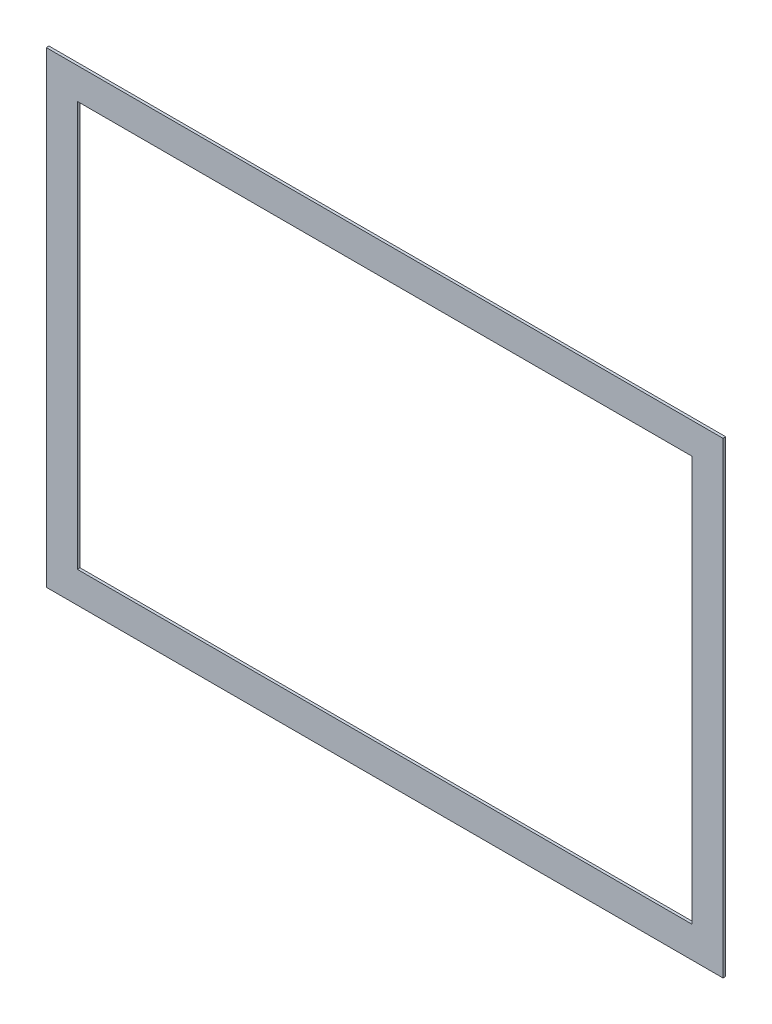
SolidWorks part; units mm, degrees
ref_plane "Front Plane" through (0, 0, 0) normal (0, 0, 1) x (1, 0, 0)
ref_plane "Top Plane" through (0, 0, 0) normal (0, 1, 0) x (1, 0, 0)
ref_plane "Right Plane" through (0, 0, 0) normal (1, 0, 0) x (0, 0, -1)
sketch "Çizim1" plane through (0, 0, 0) normal (0, 0, 1) x (1, 0, 0)
  line L0 (-23, 323) -> (478, 323)
  line L1 (0, 300) -> (455, 300)
  line L2 (0, 300) -> (0, 0)
  line L3 (0, 0) -> (455, 0)
  line L4 (455, 300) -> (455, 0)
  line L5 (478, 323) -> (478, -23)
  line L6 (-23, -23) -> (478, -23)
  line L7 (-23, 323) -> (-23, -23)
  dimension "D1" = 455
  dimension "D2" = 300
  dimension "D3" = 23
base flange "Taban-Flanş1" sketch "Çizim1" thickness 2 reverse thickness direction no parameters "D1"=0.7366
sketch "Büküm-Çizgileri1" [suppressed] plane through (0, 0, 0) normal (0, 1, 0) x (1, 0, 0)
sketch "Sınırlandırma-Kutusu1" [suppressed] plane through (0, 0, 0) normal (0, 1, 0) x (1, 0, 0)
sheet metal parameters "Sac-Levha1" thickness 2 parameters "D1"=0.7366
flat pattern "Düz-Çoğaltma1" [suppressed]
sketch "Büküm-Çizgileri2" plane through (0, 0, 0) normal (0, 1, 0) x (1, 0, 0)
sketch3d "Sınırlandırma-Kutusu2" [suppressed]
  line L0 (23, -23, 0) -> (-478, -23, 0) construction
  line L1 (23, 323, 0) -> (-478, 323, 0) construction
  line L2 (23, -23, 0) -> (23, 323, 0) construction
  line L3 (-478, -23, 0) -> (-478, 323, 0) construction
